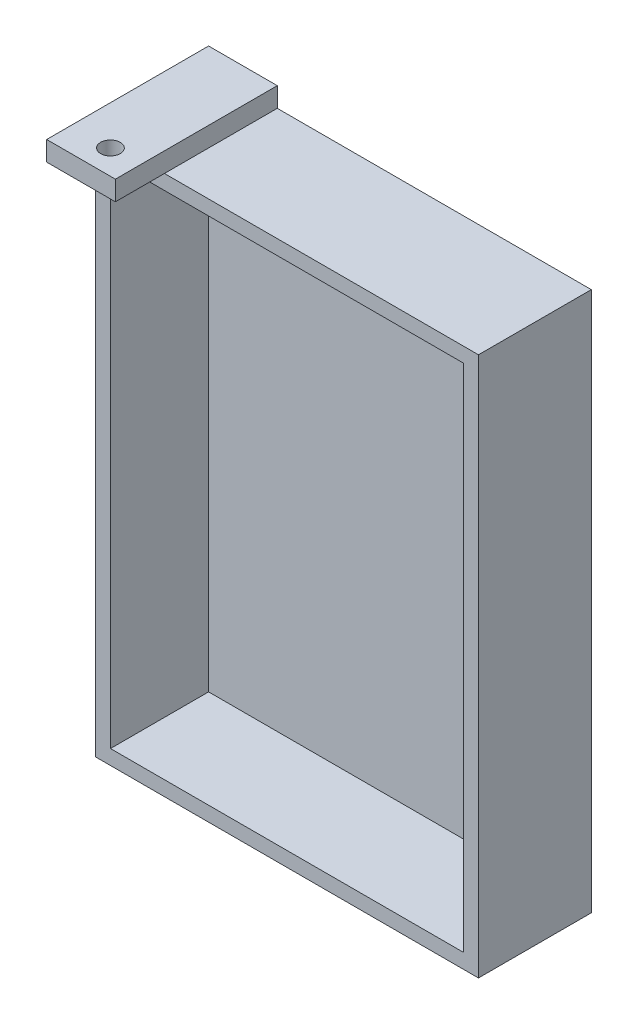
SolidWorks part; units mm, degrees
ref_plane "前视基准面" through (0, 0, 0) normal (0, 0, 1) x (1, 0, 0)
ref_plane "上视基准面" through (0, 0, 0) normal (0, 1, 0) x (1, 0, 0)
ref_plane "右视基准面" through (0, 0, 0) normal (1, 0, 0) x (0, 0, -1)
other "Configuration Table"
sketch "草图1" plane through (0, 0, 0) normal (0, 0, 1) x (1, 0, 0)
  line L1 (19.5, 27.5) -> (-19.5, 27.5)
  line L2 (19.5, 27.5) -> (19.5, -27.5)
  line L3 (19.5, -27.5) -> (-19.5, -27.5)
  line L4 (-19.5, 27.5) -> (-19.5, -27.5)
  line L5 (19.5, 27.5) -> (-19.5, -27.5) construction
  line L6 (19.5, -27.5) -> (-19.5, 27.5) construction
  point P0 (0, 0)
  dimension "D1" = 55
  dimension "D2" = 39
extrude "凸台-拉伸1" add sketch "草图1" along normal blind 11.5
shell "抽壳1" thickness 1.5 removed face at (0, 0, 11.5)
sketch "草图2" plane through (0, 0, 0) normal (0, 0, -1) x (-1, 0, 0)
  line L0 (-19.5, 27.5) -> (19.5, 27.5) construction
  line L1 (19.5, 29.5) -> (12.5, 29.5)
  line L2 (19.5, 29.5) -> (19.5, 27.5)
  line L3 (19.5, 27.5) -> (12.5, 27.5)
  line L4 (12.5, 29.5) -> (12.5, 27.5)
  line L6 (19.5, 27.5) -> (19.5, -27.5) construction
  dimension "D2" = 2
  dimension "D3" = 7
extrude "凸台-拉伸2" add sketch "草图2" against normal offset from surface (16.5 mm away) 5 separate body up to face at (0, 0, 11.5) offset beyond the face yes
sketch "草图3" plane through (0, 29.5, 0) normal (0, 1, 0) x (1, 0, 0)
  circle A0 centre (-15.502, -14) radius 1
  dimension "D1" = 2
extrude "切除-拉伸1" cut sketch "草图3" against normal up to next (2 mm away)
